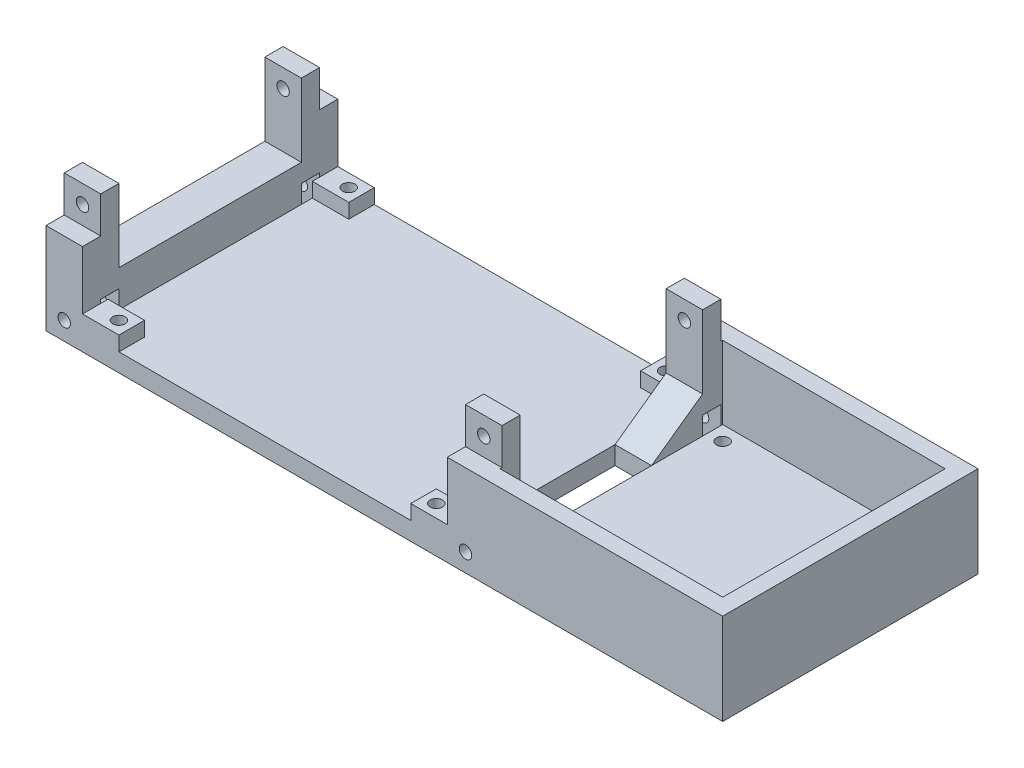
SolidWorks part; units mm, degrees
ref_plane "Front Plane" through (0, 0, 0) normal (0, 0, 1) x (1, 0, 0)
ref_plane "Top Plane" through (0, 0, 0) normal (0, 1, 0) x (1, 0, 0)
ref_plane "Right Plane" through (0, 0, 0) normal (1, 0, 0) x (0, 0, -1)
sketch "Sketch1" plane through (0, 0, 0) normal (0, 1, 0) x (1, 0, 0)
  line L1 (-60, -35) -> (60, -35)
  line L2 (-60, -35) -> (-60, 35)
  line L3 (-60, 35) -> (60, 35)
  line L4 (60, -35) -> (60, 35)
  line L5 (-60, -35) -> (60, 35) construction
  line L6 (-60, 35) -> (60, -35) construction
  point P0 (0, 0)
  dimension "D1" = 120
  dimension "D2" = 70
extrude "Boss-Extrude1" add sketch "Sketch1" along normal blind 5
sketch "Sketch4" plane through (0, 5, 0) normal (0, 1, 0) x (1, 0, 0)
  line L1 (-60, -35) -> (-50, -35)
  line L2 (-60, -35) -> (-60, -25)
  line L3 (-60, -25) -> (-50, -25)
  line L4 (-50, -35) -> (-50, -25)
  line L5 (-60, 35) -> (-50, 35)
  line L6 (-60, 35) -> (-60, 25)
  line L7 (-60, 25) -> (-50, 25)
  line L8 (-50, 35) -> (-50, 25)
  line L9 (60, -35) -> (50, -35)
  line L10 (60, -35) -> (60, -25)
  line L11 (60, -25) -> (50, -25)
  line L12 (50, -35) -> (50, -25)
  line L13 (60, 35) -> (50, 35)
  line L14 (60, 35) -> (60, 25)
  line L15 (60, 25) -> (50, 25)
  line L16 (50, 35) -> (50, 25)
  dimension "D1" = 10
  dimension "D2" = 10
extrude "Boss-Extrude2" add sketch "Sketch4" along normal blind 30
sketch "Sketch5" plane through (0, 0, 0) normal (0, -1, 0) x (1, 0, 0)
  line L0 (-60, -35) -> (-60, 35) construction
  line L1 (-60, -30) -> (-50, -30)
  line L2 (-60, -30) -> (-60, -25)
  line L3 (-60, -25) -> (-50, -25)
  line L4 (-50, -30) -> (-50, -25)
  line L5 (60, 35) -> (60, -35) construction
  line L6 (-60, 30) -> (-50, 30)
  line L7 (-60, 30) -> (-60, 25)
  line L8 (-60, 25) -> (-50, 25)
  line L9 (-50, 30) -> (-50, 25)
  line L10 (60, 30) -> (50, 30)
  line L11 (60, 30) -> (60, 25)
  line L12 (60, 25) -> (50, 25)
  line L13 (50, 30) -> (50, 25)
  line L14 (60, -35) -> (-60, -35) construction
  line L15 (60, -30) -> (50, -30)
  line L16 (60, -30) -> (60, -25)
  line L17 (60, -25) -> (50, -25)
  line L18 (50, -30) -> (50, -25)
  line L19 (-60, 35) -> (60, 35) construction
  dimension "D1" = 10
  dimension "D2" = 5
  dimension "D3" = 5
  dimension "D4" = 5
extrude "Cut-Extrude2" cut sketch "Sketch5" against normal blind 10
sketch "Sketch11" plane through (0, 35, 0) normal (0, 1, 0) x (1, 0, 0)
  line L0 (-50, -35) -> (-50, -25) construction
  line L1 (-60, -35) -> (-50, -35)
  line L2 (-60, -35) -> (-60, -30)
  line L3 (-60, -30) -> (-50, -30)
  line L4 (-50, -35) -> (-50, -30)
  line L5 (60, -35) -> (60, -25) construction
  line L6 (50, -35) -> (60, -35)
  line L7 (50, -35) -> (50, -30)
  line L8 (50, -30) -> (60, -30)
  line L9 (60, -35) -> (60, -30)
  line L10 (60, 25) -> (60, 35) construction
  line L11 (50, 35) -> (60, 35)
  line L12 (50, 35) -> (50, 30)
  line L13 (50, 30) -> (60, 30)
  line L14 (60, 35) -> (60, 30)
  line L15 (-50, 25) -> (-50, 35) construction
  line L16 (-60, 35) -> (-50, 35)
  line L17 (-60, 35) -> (-60, 30)
  line L18 (-60, 30) -> (-50, 30)
  line L19 (-50, 35) -> (-50, 30)
extrude "Cut-Extrude4" cut sketch "Sketch11" against normal blind 10
sketch "Sketch8" plane through (0, 5, 0) normal (0, 1, 0) x (1, 0, 0)
  line L1 (-50, 35) -> (-40, 35)
  line L2 (-50, 35) -> (-50, 28)
  line L3 (-50, 28) -> (-40, 28)
  line L4 (-40, 35) -> (-40, 28)
  line L5 (-50, -35) -> (-40, -35)
  line L6 (-50, -35) -> (-50, -28)
  line L7 (-50, -28) -> (-40, -28)
  line L8 (-40, -35) -> (-40, -28)
  line L9 (50, -35) -> (40, -35)
  line L10 (50, -35) -> (50, -28)
  line L11 (50, -28) -> (40, -28)
  line L12 (40, -35) -> (40, -28)
  line L13 (50, 35) -> (40, 35)
  line L14 (50, 35) -> (50, 28)
  line L15 (50, 28) -> (40, 28)
  line L16 (40, 35) -> (40, 28)
  dimension "D1" = 7
  dimension "D2" = 10
extrude "Boss-Extrude5" add sketch "Sketch8" along normal blind 4
hole_wizard "M3 Clearance Hole2" positions "Sketch10" profile "Sketch9" hole size "M3" standard "ANSI Metric"
sketch "Sketch10" plane through (0, 9, 0) normal (0, 1, 0) x (1, 0, 0)
  line L1 (40, -35) -> (50, -35) construction
  line L2 (-50, -30) -> (-50, -28) construction
  point P0 (-43.5, -31.5)
  point P2 (-43.5, 31.5)
  point P4 (43.5, 31.5)
  point P6 (43.5, -31.5)
  dimension "D1" = 87
  dimension "D2" = 63
  dimension "D3" = 3.5
  dimension "D4" = 6.5
sketch "Sketch9" plane through (-43.5, 9, 31.5) normal (1, 0, 0) x (0, 0, 1)
  line L0 (0, 0) -> (0, 66.0215)
  line L1 (0, 66.0215) -> (1.7, 65)
  line L2 (1.7, 65) -> (1.7, 0)
  line L5 (1.7, 0) -> (0, 0)
  line L10 (0, 66.0215) -> (-1.7, 65) construction
  line L11 (0, -6.35) -> (0, 107.95) construction
  dimension "Hole Dia." = 3.4
  dimension "Hole Depth" = 65
  dimension "Drill Angle" = 118
sketch "Sketch12" plane through (0, 0, 0) normal (0, -1, 0) x (1, 0, 0)
  line L1 (125.5, 35) -> (60, 35)
  line L2 (125.5, 35) -> (125.5, -35)
  line L3 (125.5, -35) -> (60, -35)
  line L4 (60, 35) -> (60, -35)
  line L5 (125.5, 35) -> (60, -35) construction
  line L6 (125.5, -35) -> (60, 35) construction
  line L7 (60, 25) -> (60, -25) construction
  point P0 (92.75, 0)
  dimension "D1" = 65.5
  dimension "D2" = 70
extrude "Boss-Extrude6" add sketch "Sketch12" against normal blind 5
sketch "Sketch13" plane through (0, 5, 0) normal (0, 1, 0) x (1, 0, 0)
  line L1 (60, 35) -> (125.5, 35)
  line L2 (60, 35) -> (60, 30.5)
  line L3 (60, 30.5) -> (121, 30.5)
  line L4 (125.5, -35) -> (125.5, 35)
  line L5 (125.5, 35) -> (125.5, -35) construction
  line L6 (60, -35) -> (125.5, -35)
  line L7 (60, -35) -> (60, -30.5)
  line L8 (60, -30.5) -> (121, -30.5)
  line L11 (121, 30.5) -> (121, -30.5)
  dimension "D1" = 61
  dimension "D2" = 4.5
  dimension "D3" = 4.5
extrude "Boss-Extrude7" add sketch "Sketch13" along normal blind 20
hole_wizard "M3 Clearance Hole3" positions "Sketch15" profile "Sketch14" hole size "M3" standard "ANSI Metric"
sketch "Sketch15" plane through (0, 5, 0) normal (0, 1, 0) x (1, 0, 0)
  line L0 (121, -30.5) -> (60, -30.5) construction
  line L2 (60, -30) -> (60, -25) construction
  point P0 (117, -26.5)
  point P2 (117, 26.5)
  point P4 (64, 26.5)
  point P6 (64, -26.5)
  point P15 (60, -27.5)
  dimension "D1" = 53
  dimension "D2" = 53
  dimension "D3" = 4
  dimension "D4" = 4
sketch "Sketch14" plane through (117, 5, 26.5) normal (1, 0, 0) x (0, 0, 1)
  line L0 (0, 0) -> (0, 66.0215)
  line L1 (0, 66.0215) -> (1.7, 65)
  line L2 (1.7, 65) -> (1.7, 0)
  line L5 (1.7, 0) -> (0, 0)
  line L10 (0, 66.0215) -> (-1.7, 65) construction
  line L11 (0, -6.35) -> (0, 107.95) construction
  dimension "Hole Dia." = 3.4
  dimension "Hole Depth" = 65
  dimension "Drill Angle" = 118
sketch "Sketch24" plane through (0, 5, 0) normal (0, 1, 0) x (1, 0, 0)
  line L1 (-60, 25) -> (-50, 25)
  line L2 (-60, 25) -> (-60, -25)
  line L3 (-60, -25) -> (-50, -25)
  line L4 (-50, 25) -> (-50, -25)
  line L5 (60, -25) -> (50, -25)
  line L6 (60, -25) -> (60, 25)
  line L7 (60, 25) -> (50, 25)
  line L8 (50, -25) -> (50, 25)
extrude "Boss-Extrude10" add sketch "Sketch24" along normal blind 10
sketch "Sketch16" plane through (0, 15, 0) normal (0, 1, 0) x (1, 0, 0)
  line L0 (50, 25) -> (50, -25) construction
  line L1 (60, -11) -> (50, -11)
  line L2 (60, -11) -> (60, 11)
  line L3 (60, 11) -> (50, 11)
  line L4 (50, -11) -> (50, 11)
  line L6 (60, -30) -> (60, -25) construction
  line L9 (60, -25) -> (50, -25) construction
  line L10 (50, 25) -> (60, 25) construction
  dimension "D1" = 14
  dimension "D2" = 14
extrude "Cut-Extrude5" cut sketch "Sketch16" against normal through all
sketch "Sketch22" plane through (0, 0, 35) normal (0, 0, 1) x (1, 0, 0)
  line L0 (-60, 0) -> (125.5, 0) construction
  line L2 (-60, 25) -> (-60, 0) construction
  line L3 (50, 25) -> (50, 9) construction
  circle A0 centre (-55, 5) radius 1.7
  circle A1 centre (55, 5) radius 1.7
  dimension "D3" = 3.4
  dimension "D1" = 5
  dimension "D2" = 5
  dimension "D4" = 5
extrude "Cut-Extrude7" cut sketch "Sketch22" against normal blind 20
chamfer "Chamfer2" distance 14 distance2 10 2 edges at (55, 15, 11) (55, 15, -11) first distance on face at (53.75, 15, 18) first distance on face at (56.25, 15, -18)
sketch "Sketch25" plane through (0, 0, 0) normal (0, -1, 0) x (1, 0, 0)
  line L0 (-60, 25) -> (-50, 25) construction
  line L1 (-57.8, -20) -> (-52.2, -20)
  line L2 (-57.8, -20) -> (-57.8, -17)
  line L3 (-57.8, -17) -> (-52.2, -17)
  line L4 (-52.2, -20) -> (-52.2, -17)
  line L5 (52.2, -20) -> (57.8, -20)
  line L6 (52.2, -20) -> (52.2, -17)
  line L7 (52.2, -17) -> (57.8, -17)
  line L8 (57.8, -20) -> (57.8, -17)
  line L9 (52.2, 20) -> (57.8, 20)
  line L10 (52.2, 20) -> (52.2, 17)
  line L11 (52.2, 17) -> (57.8, 17)
  line L12 (57.8, 20) -> (57.8, 17)
  line L13 (-57.8, 20) -> (-52.2, 20)
  line L14 (-57.8, 20) -> (-57.8, 17)
  line L15 (-57.8, 17) -> (-52.2, 17)
  line L16 (-52.2, 20) -> (-52.2, 17)
  line L17 (-50, -25) -> (-60, -25) construction
  line L18 (-50, -25) -> (-60, -25) construction
  line L23 (55, 25) -> (55, -25) construction
  line L24 (50, 25) -> (60, 25) construction
  line L25 (60, -25) -> (50, -25) construction
  line L26 (-55, 25) -> (-55, -25) construction
  line L27 (-60, 25) -> (-50, 25) construction
  dimension "D1" = 3
  dimension "D2" = 5
  dimension "D3" = 5
  dimension "D4" = 5.6
  dimension "D5" = 2.8
  dimension "D6" = 2.8
extrude "Cut-Extrude8" cut sketch "Sketch25" against normal blind 8
sketch "Sketch26" plane through (0, 0, -35) normal (0, 0, -1) x (-1, 0, 0)
  circle A0 centre (-55, 5) radius 1.7
  circle A1 centre (55, 5) radius 1.7
  circle A2 centre (55, 5) radius 1.7 construction
  circle A3 centre (-55, 5) radius 1.7 construction
extrude "Cut-Extrude9" cut sketch "Sketch26" against normal blind 20
sketch "Sketch27" plane through (0, 0, -30) normal (0, 0, -1) x (-1, 0, 0)
  line L0 (-60, 25) -> (-60, 35) construction
  line L1 (-50, 35) -> (-60, 35) construction
  line L2 (50, 25) -> (50, 35) construction
  circle A0 centre (-55, 30) radius 1.7
  circle A1 centre (55, 30) radius 1.7
  dimension "D3" = 3.4
  dimension "D1" = 5
  dimension "D2" = 5
  dimension "D4" = 5
extrude "Cut-Extrude10" cut sketch "Sketch27" against normal through all
equation "\"D5@Sketch25\"=\"D4@Sketch25\"/2"
equation "\"D6@Sketch25\"=\"D5@Sketch25\""
